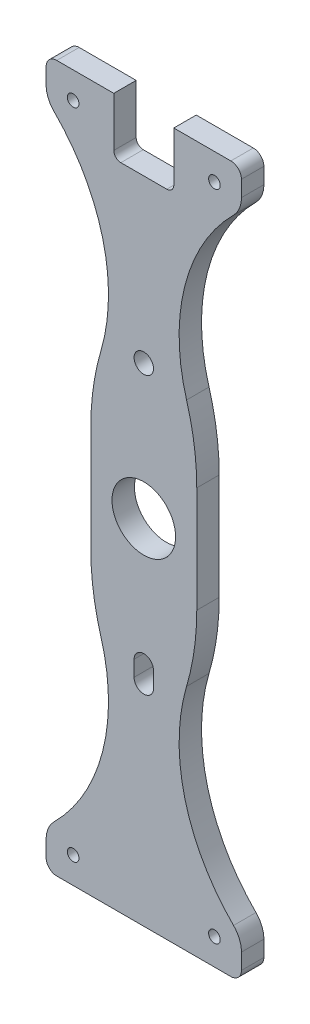
SolidWorks part; units mm, degrees
material "6061-T6 (SS)"
ref_plane "Front Plane" through (0, 0, 0) normal (0, 0, 1) x (1, 0, 0)
ref_plane "Top Plane" through (0, 0, 0) normal (0, 1, 0) x (1, 0, 0)
ref_plane "Right Plane" through (0, 0, 0) normal (1, 0, 0) x (0, 0, -1)
sketch "Sketch1" plane through (0, 0, 0) normal (0, 0, 1) x (1, 0, 0)
  line L5 (-15, 0) -> (15, 0) construction
  line L6 (0, -35.8891) -> (0, -40.3109) construction
  line L10 (2.75, -35.8891) -> (2.75, -40.3109)
  line L13 (240, 100) -> (240, -100) construction
  line L14 (-2.75, -35.8891) -> (-2.75, -40.3109)
  line L15 (-15, 15) -> (-15, -15)
  line L18 (-24.65, -100) -> (24.65, -100)
  line L21 (15, -15) -> (15, 15)
  line L23 (27.65, 92.5) -> (27.65, 97)
  line L24 (24.65, 100) -> (-24.65, 100)
  line L25 (-27.65, 97) -> (-27.65, 92.5)
  line L27 (27.65, -92.5) -> (27.65, -97)
  line L28 (-27.65, -97) -> (-27.65, -92.5)
  line L29 (-3.92, 79.4898) -> (-3.92, -120.5102) construction
  line L30 (0, 100) -> (0, 0) construction
  line L31 (-10, -49.8891) -> (-10, -92.5) construction
  line L32 (-10, -92.5) -> (10, -92.5) construction
  line L33 (10, -92.5) -> (10, -49.8891) construction
  line L34 (25.4094, 87.0906) -> (0, 61.6813) construction
  circle A0 centre (0, 0) radius 9
  circle A13 centre (0, 38.1) radius 4.9609 construction
  circle A14 centre (0, -38.1) radius 4.9609 construction
  circle A18 centre (0, 38.1) radius 2.75
  arc A19 (2.75, -35.8891) -> (-2.75, -35.8891) centre (0, -35.8891) ccw
  arc A20 (-2.75, -40.3109) -> (2.75, -40.3109) centre (0, -40.3109) ccw
  circle A21 centre (20, 92.5) radius 1.65
  circle A22 centre (-20, 92.5) radius 1.65
  circle A23 centre (-20, -92.5) radius 1.65
  circle A24 centre (20, -92.5) radius 1.65
  arc A25 (-27.65, 92.5) -> (-25.4094, 87.0906) centre (-20, 92.5) ccw
  arc A27 (27.65, 92.5) -> (25.4094, 87.0906) centre (20, 92.5) cw
  arc A29 (27.65, -92.5) -> (25.4094, -87.0906) centre (20, -92.5) ccw
  arc A32 (-27.65, -92.5) -> (-25.4094, -87.0906) centre (-20, -92.5) cw
  arc A33 (15, -15) -> (12.1176, -35.1132) centre (-56.6143, -15) cw
  arc A34 (12.1176, -35.1132) -> (25.4094, -87.0906) centre (62.6109, -49.8891) ccw
  arc A35 (-12.1176, -35.1132) -> (-25.4094, -87.0906) centre (-62.6109, -49.8891) cw
  arc A36 (-15, -15) -> (-12.1176, -35.1132) centre (56.6143, -15) ccw
  arc A37 (-15, 15) -> (-12.1176, 35.1132) centre (56.6143, 15) cw
  arc A38 (-12.1176, 35.1132) -> (-25.4094, 87.0906) centre (-62.6109, 49.8891) ccw
  arc A39 (12.1176, 35.1132) -> (25.4094, 87.0906) centre (62.6109, 49.8891) cw
  arc A40 (15, 15) -> (12.1176, 35.1132) centre (-56.6143, 15) ccw
  arc A42 (-24.65, 100) -> (-27.65, 97) centre (-24.65, 97) ccw
  arc A43 (27.65, 97) -> (24.65, 100) centre (24.65, 97) ccw
  arc A44 (-27.65, -97) -> (-24.65, -100) centre (-24.65, -97) ccw
  arc A45 (27.65, -97) -> (24.65, -100) centre (24.65, -97) cw
  point P6 (0, -38.1)
  point P64 (0, -92.5)
  point P69 (-27.65, 100)
  point P72 (27.65, 100)
  point P75 (-27.65, -100)
  point P78 (27.65, -100)
  dimension "D1" = 18
  dimension "D9" = 9.9219
  dimension "D2" = 5.5
  dimension "D3" = 3.3
  dimension "D11" = 3
  dimension "D8" = 76.2
  dimension "D4" = 220
  dimension "D6" = 185
  dimension "D7" = 200
  dimension "D10" = 6
  dimension "D5" = 40
  dimension "D13" = 30
  dimension "D14" = 20
  dimension "D15" = 30
  dimension "D16" = 45
extrude "Boss-Extrude1" add sketch "Sketch1" along normal blind 6.35
sketch "Sketch2" plane through (0, 0, 0) normal (0, 0, -1) x (-1, 0, 0)
  line L0 (-16.1644, 74.6) -> (16.1644, 74.6)
  line L1 (-24.65, 100) -> (24.65, 100) construction
  line L2 (55, 0) -> (-55, 0) construction
  line L3 (-16.1644, -74.6) -> (16.1644, -74.6)
  arc A0 (25.4094, 87.0906) -> (12.1176, 35.1132) centre (62.6109, 49.8891) ccw construction
  arc A1 (-12.1176, 35.1132) -> (-25.4094, 87.0906) centre (-62.6109, 49.8891) ccw construction
  dimension "D1" = 25.4
split line "Split Line1"
sketch "Sketch3" plane through (0, 0, 6.35) normal (0, 0, 1) x (1, 0, 0)
  line L0 (24.65, 100) -> (-24.65, 100) construction
  line L1 (-7.5, 100) -> (7.5, 100) construction
  line L2 (-7.5, 100) -> (-7.5, 85) construction
  line L3 (-7.5, 85) -> (7.5, 85) construction
  line L4 (7.5, 100) -> (7.5, 85) construction
  line L5 (-8.5, 101) -> (-8.5, 86)
  line L6 (-6.5, 84) -> (6.5, 84)
  line L7 (8.5, 101) -> (8.5, 86)
  line L9 (-8.5, 101) -> (8.5, 101) construction
  line L10 (-8.5, 84) -> (8.5, 84) construction
  line L11 (8.5, 101) -> (8.5, 84) construction
  line L12 (-8.5, 101) -> (-8.5, 84) construction
  line L13 (-8.5, 101) -> (8.5, 101)
  arc A0 (6.5, 84) -> (8.5, 86) centre (6.5, 86) ccw
  arc A1 (-8.5, 86) -> (-6.5, 84) centre (-6.5, 86) ccw
  point P6 (0, 100)
  dimension "D3" = 2
  dimension "D1" = 15
  dimension "D2" = 1
extrude "Cut-Extrude1" cut sketch "Sketch3" against normal blind 10
equation "\"frame inside height\"= 200mm'`"
equation "\"hole spacing\"= 20mm"
equation "\"top hole to bottom hole\"= \"frame inside height\" - 7.5mm * 2"
equation "\"D6@Sketch1\"=\"top hole to bottom hole\""
equation "\"D7@Sketch1\"=\"frame inside height\""
equation "\"D5@Sketch1\"=\"hole spacing\"*2"
